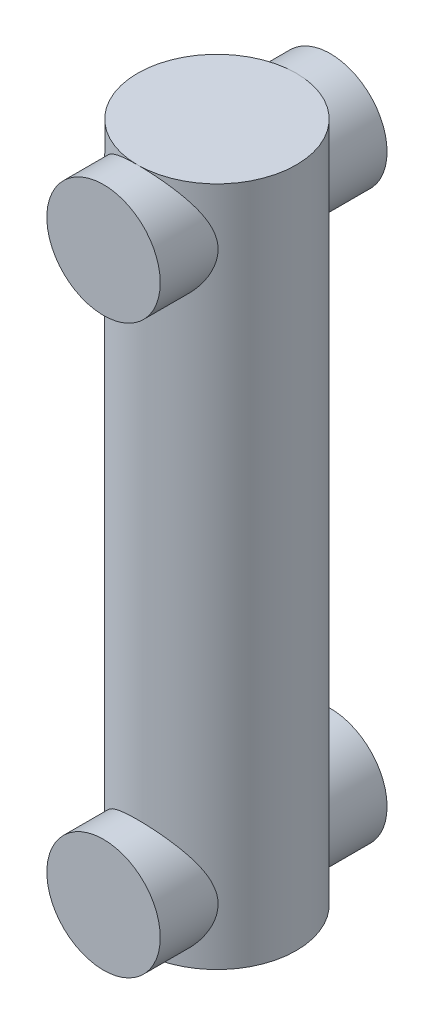
SolidWorks part; units mm, degrees
ref_plane "Ebene vorne" through (0, 0, 0) normal (0, 0, 1) x (1, 0, 0)
ref_plane "Ebene oben" through (0, 0, 0) normal (0, 1, 0) x (1, 0, 0)
ref_plane "Ebene rechts" through (0, 0, 0) normal (1, 0, 0) x (0, 0, -1)
sketch "Skizze1" plane through (0, 0, 0) normal (0, 1, 0) x (1, 0, 0)
  circle A0 centre (0, 0) radius 35
extrude "Aufsatz-Linear austragen1" add sketch "Skizze1" along normal blind 300
sketch "Skizze2" plane through (0, 0, 0) normal (0, 0, 1) x (1, 0, 0)
  line L0 (-35, 0) -> (35, 0) construction
  line L1 (35, 300) -> (-35, 300) construction
  circle A0 centre (0, 25) radius 25
  circle A1 centre (0, 275) radius 25
  dimension "D1" = 50
  dimension "D3" = 25
  dimension "D4" = 50
  dimension "D2" = 25
extrude "Aufsatz-Linear austragen2" add sketch "Skizze2" along normal blind 50 and the other way blind 50
